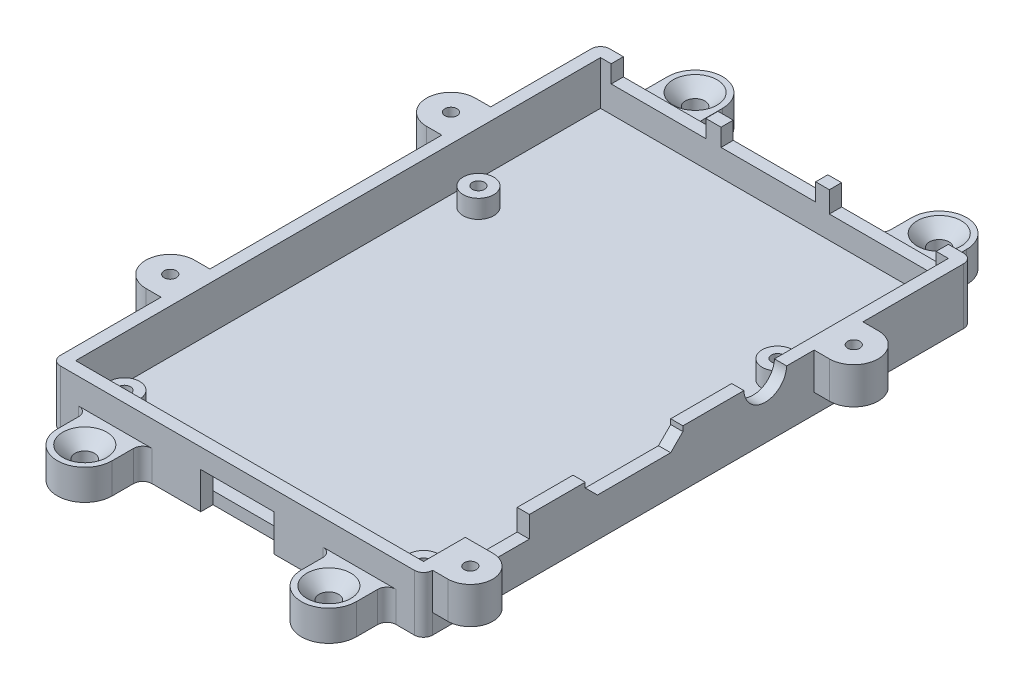
SolidWorks part; units mm, degrees
ref_plane "Спереди" through (0, 0, 0) normal (0, 0, 1) x (1, 0, 0)
ref_plane "Сверху" through (0, 0, 0) normal (0, 1, 0) x (1, 0, 0)
ref_plane "Справа" through (0, 0, 0) normal (1, 0, 0) x (0, 0, -1)
sketch "Эскиз1" plane through (0, 0, 0) normal (0, 1, 0) x (1, 0, 0)
  line L0 (0, 45) -> (0, -45) construction
  line L1 (-30.5, 45) -> (30.5, 45)
  line L2 (-30.5, 45) -> (-30.5, -45)
  line L3 (-30.5, -45) -> (30.5, -45)
  line L4 (30.5, 45) -> (30.5, -45)
  line L6 (-30.5, 0) -> (30.5, 0) construction
  point P8 (0, 0)
  dimension "D1" = 61
  dimension "D2" = 90
extrude "тело" add sketch "Эскиз1" along normal blind 9.2
sketch "Эскиз2" plane through (0, 9.2, 0) normal (0, 1, 0) x (1, 0, 0)
  line L0 (-28.5, -43) -> (28.5, 43) construction
  line L1 (-28.5, 43) -> (28.5, 43)
  line L2 (-28.5, 43) -> (-28.5, -43)
  line L3 (-28.5, -43) -> (28.5, -43)
  line L4 (28.5, 43) -> (28.5, -43)
  line L5 (0, 45) -> (0, -45) construction
  line L6 (30.5, 45) -> (-30.5, 45) construction
  line L7 (-30.5, -45) -> (30.5, -45) construction
  line L9 (-30.5, 45) -> (-30.5, -45) construction
  line L10 (-30.5, 0) -> (30.5, 0) construction
  line L11 (30.5, -45) -> (30.5, 45) construction
  point P16 (0, 0)
  dimension "D1" = 86
  dimension "D2" = 57
extrude "углубление под плату" cut sketch "Эскиз2" against normal blind 7.2
sketch "Эскиз3" plane through (0, 2, 0) normal (0, 1, 0) x (1, 0, 0)
  line L0 (0, 43) -> (0, -43) construction
  line L1 (-24.5, 19) -> (24.5, 19) construction
  line L2 (-24.5, 19) -> (-24.5, -39) construction
  line L3 (-24.5, -39) -> (24.5, -39) construction
  line L4 (24.5, 19) -> (24.5, -39) construction
  line L5 (28.5, 43) -> (-28.5, 43) construction
  line L6 (-28.5, -43) -> (28.5, -43) construction
  circle A0 centre (-24.5, 19) radius 2.5
  circle A1 centre (24.5, 19) radius 2.5
  circle A2 centre (24.5, -39) radius 2.5
  circle A3 centre (-24.5, -39) radius 2.5
  circle A4 centre (-24.5, 19) radius 1
  circle A5 centre (24.5, 19) radius 1
  circle A6 centre (24.5, -39) radius 1
  circle A7 centre (-24.5, -39) radius 1
  point P14 (0, -39)
  dimension "D4" = 5
  dimension "D5" = 2
  dimension "D1" = 49
  dimension "D2" = 58
  dimension "D3" = 4
extrude "стойки" add sketch "Эскиз3" along normal blind 3
sketch "Эскиз4" plane through (30.5, 0, 0) normal (1, 0, 0) x (0, 0, -1)
  line L0 (-45, 0) -> (45, 0) construction
  line L1 (-36.15, 9.7) -> (-27.65, 9.7)
  line L2 (-36.15, 9.7) -> (-36.15, 5.7)
  line L3 (-36.15, 5.7) -> (-27.65, 5.7)
  line L4 (-27.65, 9.7) -> (-27.65, 5.7)
  line L6 (-45, 9.2) -> (-45, 0) construction
  dimension "D1" = 8.5
  dimension "D2" = 4
  dimension "D3" = 5.7
  dimension "D4" = 8.85
extrude "отверстие под microusb" cut sketch "Эскиз4" against normal up to surface (2 mm away) up to face at (28.5, 5.6, 0)
sketch "Эскиз5" plane through (30.5, 0, 0) normal (1, 0, 0) x (0, 0, -1)
  line L0 (-45, 0) -> (45, 0) construction
  line L1 (-18.5, 12.43) -> (-2.5, 12.43)
  line L2 (-18.5, 12.43) -> (-18.5, 6.38)
  line L3 (-18.5, 6.38) -> (-2.5, 6.38)
  line L4 (-2.5, 12.43) -> (-2.5, 6.38)
  line L5 (-45, 9.2) -> (-45, 0) construction
  dimension "D1" = 16
  dimension "D2" = 6.05
  dimension "D3" = 6.38
  dimension "D4" = 26.5
extrude "отверстие под hdmi" cut sketch "Эскиз5" against normal up to surface (2 mm away) up to face at (28.5, 6.525, 15.95)
sketch "Эскиз6" plane through (30.5, 0, 0) normal (1, 0, 0) x (0, 0, -1)
  line L0 (-45, 9.2) -> (-45, 0) construction
  line L1 (-45, 0) -> (45, 0) construction
  circle A0 centre (11, 9.3) radius 3.5
  dimension "D1" = 7
  dimension "D2" = 56
  dimension "D3" = 9.3
extrude "отверстие под аудио" cut sketch "Эскиз6" against normal up to surface (2 mm away) up to face at (28.5, 6.9467, 14.1333)
sketch "Эскиз7" plane through (0, 0, -45) normal (0, 0, -1) x (-1, 0, 0)
  line L0 (-30.5, 9.2) -> (-30.5, 0) construction
  line L1 (-26.5, 19.75) -> (-9, 19.75)
  line L2 (-26.5, 19.75) -> (-26.5, 5.75)
  line L3 (-26.5, 5.75) -> (-9, 5.75)
  line L4 (-9, 19.75) -> (-9, 5.75)
  line L5 (-30.5, 0) -> (30.5, 0) construction
  dimension "D1" = 17.5
  dimension "D2" = 14
  dimension "D3" = 4
  dimension "D4" = 19.75
extrude "отверстие под ethernet" cut sketch "Эскиз7" against normal up to surface (2 mm away) up to face at (0, 5.6, -43)
sketch "Эскиз8" plane through (0, 0, -45) normal (0, 0, -1) x (-1, 0, 0)
  line L0 (-30.5, 9.2) -> (-30.5, 0) construction
  line L1 (-6.75, 22.45) -> (8.75, 22.45)
  line L2 (-6.75, 22.45) -> (-6.75, 6.33)
  line L3 (-6.75, 6.33) -> (8.75, 6.33)
  line L4 (8.75, 22.45) -> (8.75, 6.33)
  line L5 (-30.5, 0) -> (30.5, 0) construction
  dimension "D1" = 15.5
  dimension "D2" = 16.12
  dimension "D3" = 23.75
  dimension "D4" = 22.45
extrude "отверстие под usb" cut sketch "Эскиз8" against normal up to surface (2 mm away) up to face at (8.875, 6.5375, -43)
pattern_linear "Линейный массив1" count 2 spacing 18 along (-1, 0, 0) of "отверстие под usb"
sketch "Эскиз9" plane through (0, 0, 45) normal (0, 0, 1) x (1, 0, 0)
  line L1 (-6, 6) -> (6, 6)
  line L2 (-6, 6) -> (-6, 0)
  line L3 (-6, 0) -> (6, 0)
  line L4 (6, 6) -> (6, 0)
  point P4 (0, 0)
  dimension "D1" = 12
  dimension "D2" = 6
extrude "отверстие под microsd" cut sketch "Эскиз9" against normal up to surface (2 mm away) up to face at (0, 5.6, 43)
sketch "Эскиз10" plane through (0, 0, 0) normal (0, -1, 0) x (1, 0, 0)
  line L0 (-35, 44.5) -> (-30.5, 44.5) construction
  line L1 (-30.5, -45) -> (-30.5, 45) construction
  line L2 (-35, 35.5) -> (-30.5, 35.5) construction
  line L3 (-30.5, 44.5) -> (-30.5, 35.5) construction
  line L4 (0, 0) -> (0, 45) construction
  line L5 (6, 45) -> (-6, 45) construction
  line L6 (-30.5, 0) -> (30.5, 0) construction
  line L7 (30.5, 45) -> (30.5, -45) construction
  line L8 (-24.5, 50) -> (-24.5, 45)
  line L9 (-30.5, 45) -> (-6, 45) construction
  line L10 (-15.5, 50) -> (-15.5, 45)
  line L11 (-15.5, 45) -> (-24.5, 45)
  arc A0 (-35, 44.5) -> (-35, 35.5) centre (-35, 40) ccw construction
  circle A1 centre (-35, 40) radius 1.6 construction
  circle A2 centre (-20, 50) radius 1.6
  arc A3 (-15.5, 50) -> (-24.5, 50) centre (-20, 50) ccw
  dimension "D1" = 4.5
  dimension "D2" = 3.2
  dimension "D5" = 3.2
  dimension "D6" = 4.5
  dimension "D3" = 35
  dimension "D4" = 40
  dimension "D7" = 20
  dimension "D8" = 50
extrude "крепежное ухо" add sketch "Эскиз10" against normal blind 5
mirror "Зеркальное отражение1" about plane through (0, 0, 0) normal (1, 0, 0) of "крепежное ухо"
mirror "Зеркальное отражение2" about plane through (0, 0, 0) normal (0, 0, 1) of "Зеркальное отражение1"
chamfer "Фаска1" distance 2 angle 45 2 edges at (29.5, 6.38, 2.5) (29.5, 6.38, 18.5)
fillet "Скругление2" radius 1.5 12 edges at (30.5, 4.6, -45) (-30.5, 4.6, -45) (-30.5, 4.6, 45) (30.5, 4.6, 45) (-24.5, 2.5, 45) (-15.5, 2.5, 45) (15.5, 2.5, 45) (24.5, 2.5, 45) (15.5, 2.5, -45) (24.5, 2.5, -45) (-15.5, 2.5, -45) (-24.5, 2.5, -45)
sketch "Эскиз11" plane through (0, 9.2, 0) normal (0, 1, 0) x (1, 0, 0)
  line L0 (-33, 27) -> (-30.5, 27)
  line L1 (-30.5, 43.5) -> (-30.5, -43.5) construction
  line L2 (-33, 19) -> (-30.5, 19)
  line L3 (-30.5, 19) -> (-30.5, 27)
  line L4 (0, -45) -> (0, 45) construction
  line L5 (-29, -45) -> (29, -45) construction
  line L6 (6.75, 45) -> (-8.75, 45) construction
  line L7 (30.5, 19) -> (30.5, 27)
  line L8 (-30.5, 0) -> (30.5, 0) construction
  line L9 (30.5, -2.5) -> (30.5, 7.5014) construction
  line L10 (33, 19) -> (30.5, 19)
  line L11 (33, 27) -> (30.5, 27)
  line L12 (-30.5, -19) -> (-30.5, -27)
  line L13 (-33, -19) -> (-30.5, -19)
  line L14 (-33, -27) -> (-30.5, -27)
  line L15 (30.5, -43.5) -> (30.5, -36.15)
  line L16 (33, -43.5) -> (30.5, -43.5)
  line L17 (33, -36.15) -> (30.5, -36.15)
  line L18 (28.5, -36.15) -> (30.5, -36.15) construction
  arc A0 (-33, 27) -> (-33, 19) centre (-33, 23) ccw
  circle A1 centre (-33, 23) radius 1
  circle A2 centre (33, 23) radius 1
  arc A3 (33, 27) -> (33, 19) centre (33, 23) cw
  circle A4 centre (-33, -23) radius 1
  arc A5 (-33, -27) -> (-33, -19) centre (-33, -23) cw
  circle A6 centre (33, -39.825) radius 1
  arc A7 (33, -36.15) -> (33, -43.5) centre (33, -39.825) cw
  dimension "D1" = 4
  dimension "D2" = 2
  dimension "D3" = 33
  dimension "D4" = 23
extrude "наплывы крепления крышки" add sketch "Эскиз11" against normal blind 6
chamfer "Фаска2" distance 2 angle 45 4 edges at (20, 5, -48.4) (-20, 5, -48.4) (20, 5, 48.4) (-20, 5, 48.4)
